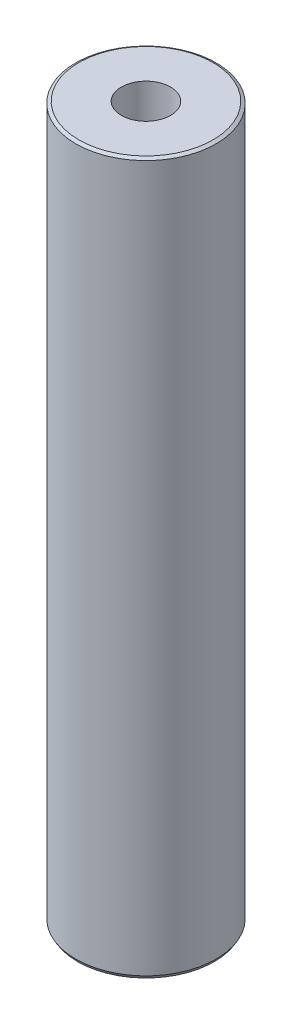
SolidWorks part; units mm, degrees
ref_plane "Front Plane" through (0, 0, 0) normal (0, 0, 1) x (1, 0, 0)
ref_plane "Top Plane" through (0, 0, 0) normal (0, 1, 0) x (1, 0, 0)
ref_plane "Right Plane" through (0, 0, 0) normal (1, 0, 0) x (0, 0, -1)
sketch "Sketch1" plane through (0, 0, 0) normal (0, 1, 0) x (1, 0, 0)
  circle A0 centre (0, 0) radius 52.5
  dimension "SHAFT_OD" = 105
extrude "Boss-Extrude1" add sketch "Sketch1" along normal blind 531.7585
sketch "Sketch2" plane through (0, 0, 0) normal (0, 1, 0) x (1, 0, 0)
  circle A0 centre (0, 0) radius 18.409
  dimension "BORE_D" = 36.8181
extrude "Cut-Extrude1" cut sketch "Sketch2" along normal through all
chamfer "Chamfer1" distance 1.3584 angle 60 2 edges at (0, 531.7585, 52.5) (0, 0, 52.5) first distance on face at (0, 531.7585, 52.5) first distance on face at (0, 0, 18.409)
